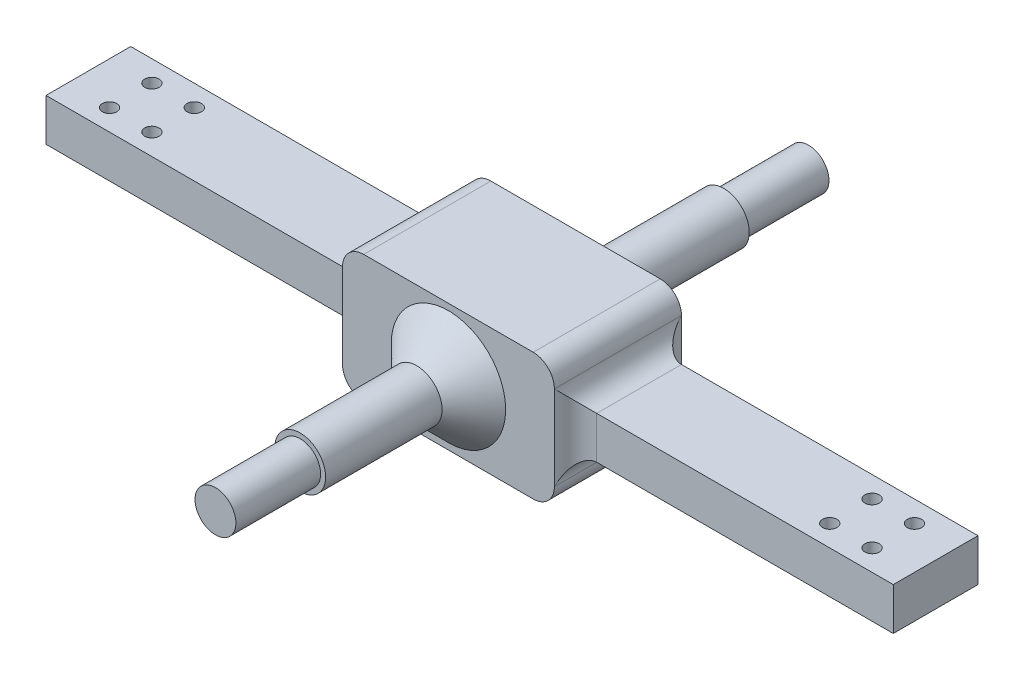
SolidWorks part; units mm, degrees
material "PEI"
ref_plane "Front Plane" through (0, 0, 0) normal (0, 0, 1) x (1, 0, 0)
ref_plane "Top Plane" through (0, 0, 0) normal (0, 1, 0) x (1, 0, 0)
ref_plane "Right Plane" through (0, 0, 0) normal (1, 0, 0) x (0, 0, -1)
sketch "Sketch1" plane through (0, 0, 0) normal (0, 1, 0) x (1, 0, 0)
  line L1 (-100, -10) -> (100, -10)
  line L2 (-100, -10) -> (-100, 10)
  line L3 (-100, 10) -> (100, 10)
  line L4 (100, -10) -> (100, 10)
  line L5 (-100, -10) -> (100, 10) construction
  line L6 (-100, 10) -> (100, -10) construction
  point P0 (0, 0)
  dimension "D1" = 200
  dimension "D2" = 20
extrude "Boss-Extrude1" add sketch "Sketch1" along normal mid plane 10
sketch "Sketch2" plane through (0, 0, 0) normal (0, 0, 1) x (1, 0, 0)
  line L1 (-25, -15) -> (25, -15)
  line L2 (-25, -15) -> (-25, 15)
  line L3 (-25, 15) -> (25, 15)
  line L4 (25, -15) -> (25, 15)
  line L5 (-25, -15) -> (25, 15) construction
  line L6 (-25, 15) -> (25, -15) construction
  point P0 (0, 0)
  dimension "D1" = 50
  dimension "D2" = 30
extrude "Boss-Extrude2" add sketch "Sketch2" along normal mid plane 30
fillet "Fillet3" radius 5 12 edges at (25, -15, 0) (-25, -15, 0) (25, 15, 0) (-25, 15, 0) (25, -5, 0) (25, 5, 0) (-25, -5, 0) (-25, 5, 0) (-25, 0, -10) (-25, 0, 10) (25, 0, -10) (25, 0, 10)
sketch "Sketch3" plane through (0, 0, 0) normal (0, 0, 1) x (1, 0, 0)
  circle A0 centre (0, 0) radius 6
  dimension "D1" = 12
extrude "Boss-Extrude3" add sketch "Sketch3" along normal mid plane 100
chamfer "Chamfer1" distance 7.5 angle 45 2 edges at (-6, 0, 15) (-6, 0, -15)
hole_wizard "M3 Clearance Hole1" positions "Sketch18" profile "Sketch17" hole size "M3" standard "ANSI Metric" end condition through all
sketch "Sketch18" plane through (0, 5, 0) normal (0, 1, 0) x (1, 0, 0)
  line L0 (0, -16.5) -> (0, 16.5) construction
  line L1 (-100, 10) -> (-100, -10) construction
  point P0 (-90, 5)
  point P2 (-90, -5)
  point P10 (90, -5)
  point P11 (90, 5)
  point P16 (-80, 5)
  point P20 (-80, -5)
  point P25 (80, 5)
  point P30 (80, -5)
  dimension "D1" = 10
  dimension "D2" = 5
  dimension "D3" = 90
  dimension "D4" = 10
  dimension "D5" = 10
  dimension "D6" = 10
sketch "Sketch17" plane through (-90, 5, -5) normal (1, 0, 0) x (0, 0, 1)
  line L0 (0, 0) -> (0, 20)
  line L1 (0, 20) -> (1.7, 20)
  line L2 (1.7, 20) -> (1.7, 0)
  line L5 (1.7, 0) -> (0, 0)
  line L11 (0, -6.35) -> (0, 107.95) construction
  dimension "Thru Hole Dia." = 3.4
  dimension "Thru Hole Depth" = 20
sketch "Sketch19" plane through (0, 0, -50) normal (0, 0, -1) x (-1, 0, 0)
  circle A0 centre (0, 0) radius 4.825
  dimension "D1" = 9.65
extrude "Boss-Extrude4" add sketch "Sketch19" along normal blind 20
sketch "Sketch20" plane through (0, 0, 50) normal (0, 0, 1) x (1, 0, 0)
  circle A0 centre (0, 0) radius 4.825
  dimension "D1" = 9.65
extrude "Boss-Extrude5" add sketch "Sketch20" along normal blind 20
equation "\"BeamLength\"= 50cm"
equation "\"D1@Sketch1\"=\"BeamLength\" - 30"
equation "\"BeamWidth\"= 2cm"
equation "\"BeamHeight\"= 1cm"
equation "\"D2@Sketch1\"=\"BeamWidth\""
equation "\"D1@Boss-Extrude1\"=\"BeamHeight\""
equation "\"shaftLength\"= 10cm"
equation "\"shaftdia\"= 1.2cm"
equation "\"D1@Sketch3\"=\"shaftdia\""
equation "\"D1@Boss-Extrude3\"=\"shaftLength\""
equation "\"Mount Dia\"= 4cm"
equation "\"Motor's Diameter\"= 2.8cm"
equation "\"D1@Sketch6\"=\"Motor's Diameter\"''''''''''''''''''''''''''''"
